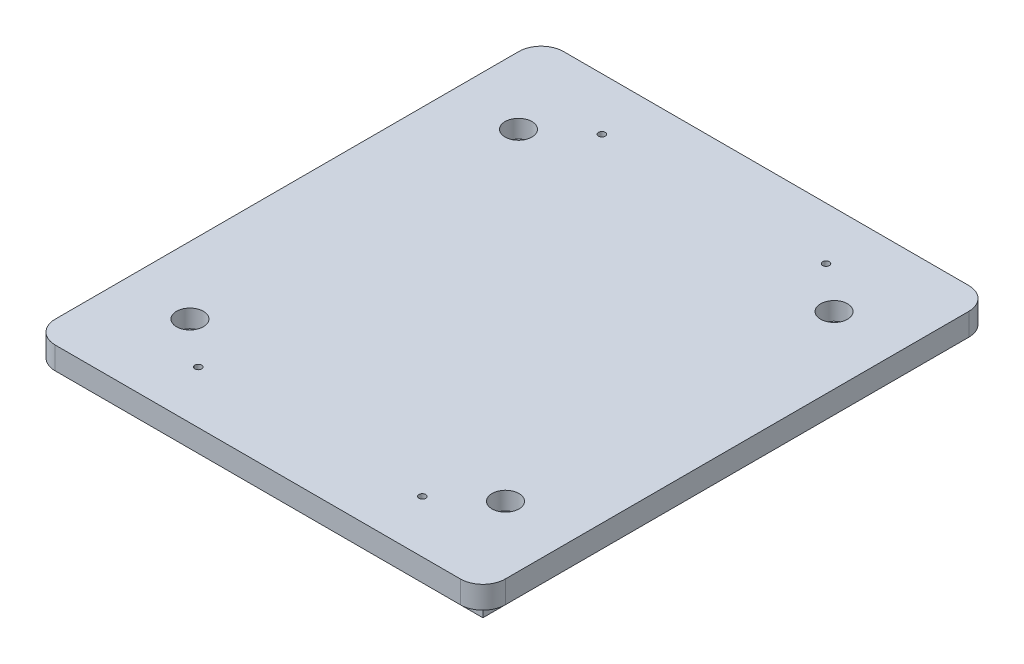
SolidWorks part; units mm, degrees
ref_plane "Front Plane" through (0, 0, 0) normal (0, 0, 1) x (1, 0, 0)
ref_plane "Top Plane" through (0, 0, 0) normal (0, 1, 0) x (1, 0, 0)
ref_plane "Right Plane" through (0, 0, 0) normal (1, 0, 0) x (0, 0, -1)
sketch "Sketch1" plane through (0, 0, 0) normal (0, 1, 0) x (1, 0, 0)
  line L1 (-50.2, -56.7) -> (50.2, -56.7)
  line L2 (-50.2, -56.7) -> (-50.2, 56.7)
  line L3 (-50.2, 56.7) -> (50.2, 56.7)
  line L4 (50.2, -56.7) -> (50.2, 56.7)
  line L5 (-50.2, -56.7) -> (50.2, 56.7) construction
  line L6 (-50.2, 56.7) -> (50.2, -56.7) construction
  point P0 (0, 0)
  dimension "D1" = 100.4
  dimension "D2" = 113.4
extrude "Boss-Extrude1" add sketch "Sketch1" along normal blind 5
sketch "Sketch2" plane through (0, 0, 0) normal (0, -1, 0) x (1, 0, 0)
  line L0 (50.2, 56.7) -> (50.2, -56.7) construction
  line L1 (-45.2, -51.7) -> (45.2, -51.7)
  line L2 (-45.2, -51.7) -> (-45.2, 51.7)
  line L3 (-45.2, 51.7) -> (45.2, 51.7)
  line L4 (45.2, -51.7) -> (45.2, 51.7)
  line L5 (-45.2, -51.7) -> (45.2, 51.7) construction
  line L6 (-45.2, 51.7) -> (45.2, -51.7) construction
  line L8 (-50.2, 56.7) -> (50.2, 56.7) construction
  point P0 (0, 0)
  dimension "D1" = 5
  dimension "D2" = 5
extrude "Boss-Extrude2" add sketch "Sketch2" along normal blind 5
fillet "Fillet1" radius 5 4 edges at (-50.2, 2.5, -56.7) (50.2, 2.5, -56.7) (50.2, 2.5, 56.7) (-50.2, 2.5, 56.7)
sketch "Sketch3" plane through (0, 5, 0) normal (0, 1, 0) x (1, 0, 0)
  line L0 (45.2, 56.7) -> (-45.2, 56.7) construction
  line L1 (-50.2, 51.7) -> (-50.2, -51.7) construction
  circle A0 centre (-35.2, 36.65) radius 1.5
  circle A1 centre (-35.2, -36.65) radius 1.5
  circle A2 centre (35.2, 36.65) radius 1.5
  circle A3 centre (35.2, -36.65) radius 1.5
  dimension "D1" = 73.3
  dimension "D5" = 20.05
  dimension "D2" = 73.3
  dimension "D3" = 70.4
  dimension "D4" = 70.4
  dimension "D6" = 15
extrude "Cut-Extrude1" cut sketch "Sketch3" against normal blind 17
sketch "Sketch4" plane through (0, 5, 0) normal (0, 1, 0) x (1, 0, 0)
  circle A0 centre (-35.2, 36.65) radius 3
  circle A1 centre (-35.2, -36.65) radius 3
  circle A2 centre (35.2, 36.65) radius 3
  circle A3 centre (35.2, -36.65) radius 3
extrude "Cut-Extrude2" cut sketch "Sketch4" against normal blind 4
sketch "Sketch5" plane through (0, 5, 0) normal (0, 1, 0) x (1, 0, 0)
  line L0 (-45.2, -56.7) -> (45.2, -56.7) construction
  line L1 (45.2, 56.7) -> (-45.2, 56.7) construction
  line L2 (-50.2, 51.7) -> (-50.2, -51.7) construction
  line L3 (50.2, -51.7) -> (50.2, 51.7) construction
  circle A0 centre (-24.9457, 45) radius 0.75
  circle A1 centre (-25, -45) radius 0.75
  circle A2 centre (25.0543, 45) radius 0.75
  circle A3 centre (25, -45) radius 0.75
  point P8 (0, 0)
  point P15 (0, 0)
  dimension "D1" = 50
  dimension "D2" = 50
  dimension "D3" = 90
  dimension "D4" = 90
  dimension "D5" = 11.7
  dimension "D6" = 11.7
  dimension "D7" = 25.2543
  dimension "D8" = 25.2
extrude "Cut-Extrude3" cut sketch "Sketch5" against normal blind 19
